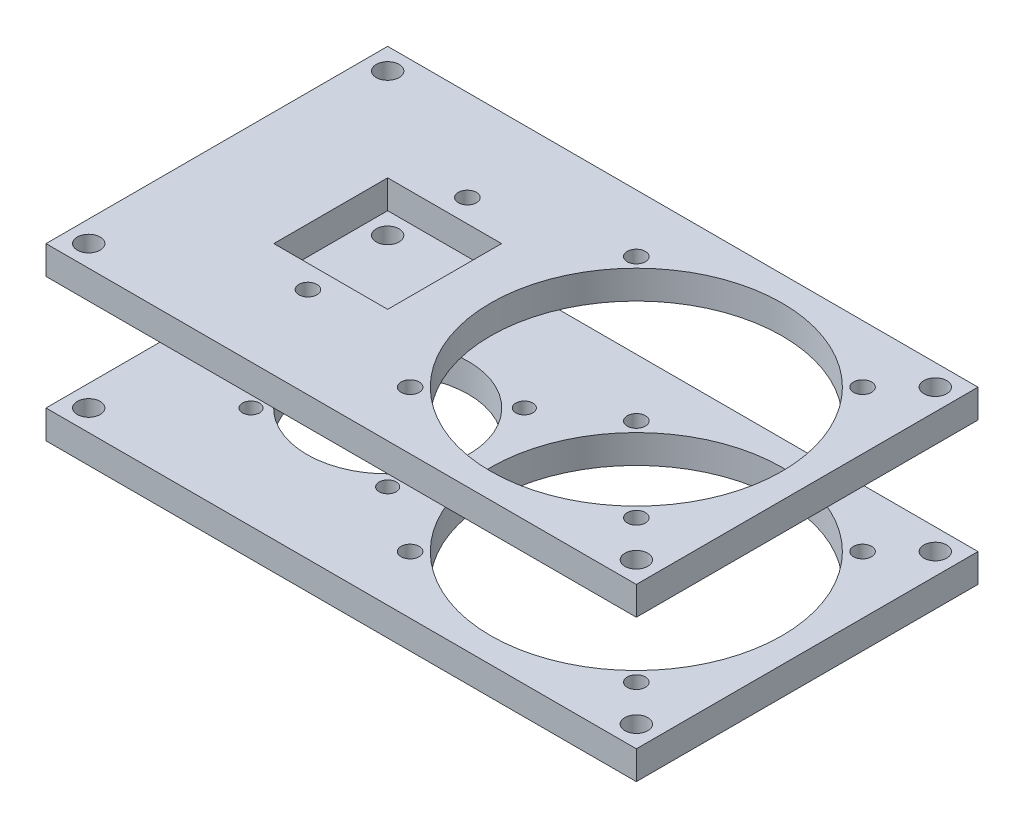
SolidWorks part; units mm, degrees
material "Alum Plate"
ref_plane "Front Plane" through (0, 0, 0) normal (0, 0, 1) x (1, 0, 0)
ref_plane "Top Plane" through (0, 0, 0) normal (0, 1, 0) x (1, 0, 0)
ref_plane "Right Plane" through (0, 0, 0) normal (1, 0, 0) x (0, 0, -1)
sketch "Sketch2" plane through (0, 0, 0) normal (0, 1, 0) x (1, 0, 0)
  line L0 (0, 0) -> (-55.4609, 0) construction
  line L2 (-93.5609, 38.1) -> (38.1, 38.1)
  line L3 (-93.5609, 38.1) -> (-93.5609, -38.1)
  line L4 (-93.5609, -38.1) -> (38.1, -38.1)
  line L5 (38.1, 38.1) -> (38.1, -38.1)
  line L6 (-93.5609, 38.1) -> (38.1, -38.1) construction
  line L7 (-93.5609, -38.1) -> (38.1, 38.1) construction
  line L8 (-68.1609, 12.7) -> (-42.7609, 12.7) construction
  line L9 (-68.1609, 12.7) -> (-68.1609, -12.7) construction
  line L10 (-68.1609, -12.7) -> (-42.7609, -12.7) construction
  line L11 (-42.7609, 12.7) -> (-42.7609, -12.7) construction
  line L12 (-68.1609, 12.7) -> (-42.7609, -12.7) construction
  line L13 (-68.1609, -12.7) -> (-42.7609, 12.7) construction
  circle A0 centre (0, 0) radius 32.5
  circle A1 centre (-55.4609, 0) radius 18 construction
  point P5 (-27.7305, 0)
  dimension "D1" = 65
  dimension "D2" = 36
  dimension "D3" = 55.4609
  dimension "D4" = 38.1
  dimension "D5" = 38.1
  dimension "D6" = 25.4
  dimension "D7" = 25.4
extrude "Boss-Extrude1" add sketch "Sketch2" against normal blind 6.35 from offset 19.05
mirror "Mirror1" about plane through (0, 0, 0) normal (0, 1, 0) of bodies 101
sketch "Sketch3" plane through (0, 19.05, 0) normal (0, 1, 0) x (1, 0, 0)
  line L1 (-68.1609, -12.7) -> (-42.7609, -12.7)
  line L2 (-68.1609, -12.7) -> (-68.1609, 12.7)
  line L3 (-68.1609, 12.7) -> (-42.7609, 12.7)
  line L4 (-42.7609, -12.7) -> (-42.7609, 12.7)
  line L5 (-68.1609, -12.7) -> (-42.7609, 12.7) construction
  line L6 (-68.1609, 12.7) -> (-42.7609, -12.7) construction
  point P4 (-55.4609, 0)
extrude "Cut-Extrude1" cut sketch "Sketch3" against normal up to next (6.35 mm away)
sketch "Sketch4" plane through (0, -19.05, 0) normal (0, -1, 0) x (1, 0, 0)
  circle A0 centre (-55.4609, 0) radius 18 construction
  circle A1 centre (-55.4609, 0) radius 18
extrude "Cut-Extrude2" cut sketch "Sketch4" against normal up to next (6.35 mm away)
sketch "Sketch5" plane through (0, -19.05, 0) normal (0, -1, 0) x (1, 0, 0)
  line L1 (-70.7009, 15.24) -> (-40.2209, 15.24) construction
  line L2 (-70.7009, 15.24) -> (-70.7009, -15.24) construction
  line L3 (-70.7009, -15.24) -> (-40.2209, -15.24) construction
  line L4 (-40.2209, 15.24) -> (-40.2209, -15.24) construction
  line L5 (-70.7009, 15.24) -> (-40.2209, -15.24) construction
  line L6 (-70.7009, -15.24) -> (-40.2209, 15.24) construction
  circle A0 centre (-70.7009, 15.24) radius 1.905
  circle A1 centre (-40.2209, 15.24) radius 1.905
  circle A2 centre (-40.2209, -15.24) radius 1.905
  circle A3 centre (-70.7009, -15.24) radius 1.905
  point P0 (-55.4609, 0)
  dimension "D2" = 3.81
  dimension "D1" = 30.48
extrude "Cut-Extrude3" cut sketch "Sketch5" against normal up to next (6.35 mm away)
sketch "Sketch6" plane through (0, 19.05, 0) normal (0, 1, 0) x (1, 0, 0)
  line L0 (-93.5609, -33.3375) -> (-88.7984, -33.3375) construction
  line L1 (-93.5609, 38.1) -> (-93.5609, -38.1) construction
  line L2 (-88.7984, -33.3375) -> (-88.7984, -38.1) construction
  line L3 (-93.5609, -38.1) -> (38.1, -38.1) construction
  line L4 (-93.5609, 33.3375) -> (-88.7984, 33.3375) construction
  line L5 (-88.7984, 33.3375) -> (-88.7984, 38.1) construction
  line L6 (38.1, 38.1) -> (-93.5609, 38.1) construction
  line L7 (38.1, 33.3375) -> (33.3375, 33.3375) construction
  line L8 (38.1, -38.1) -> (38.1, 38.1) construction
  line L9 (33.3375, 33.3375) -> (33.3375, 38.1) construction
  line L10 (33.3375, -38.1) -> (33.3375, -33.3375) construction
  line L11 (33.3375, -33.3375) -> (38.1, -33.3375) construction
  line L13 (25.226, 25.226) -> (-25.226, 25.226) construction
  line L14 (25.226, 25.226) -> (25.226, -25.226) construction
  line L15 (25.226, -25.226) -> (-25.226, -25.226) construction
  line L16 (-25.226, 25.226) -> (-25.226, -25.226) construction
  line L17 (25.226, 25.226) -> (-25.226, -25.226) construction
  line L18 (25.226, -25.226) -> (-25.226, 25.226) construction
  circle A0 centre (-88.7984, 33.3375) radius 2.5527
  circle A1 centre (33.3375, 33.3375) radius 2.5527
  circle A2 centre (33.3375, -33.3375) radius 2.5527
  circle A3 centre (-88.7984, -33.3375) radius 2.5527
  circle A4 centre (-25.226, 25.226) radius 2.0193
  circle A5 centre (25.226, 25.226) radius 2.0193
  circle A6 centre (25.226, -25.226) radius 2.0193
  circle A7 centre (-25.226, -25.226) radius 2.0193
  circle A8 centre (0, 0) radius 32.5 construction
  point P24 (0, 0)
  point P34 (-22.981, 22.981)
  point P35 (0, 0)
  point P36 (0, 0)
  dimension "D2" = 5.1054
  dimension "D3" = 4.0386
  dimension "D1" = 4.7625
  dimension "D4" = 3.175
extrude "Cut-Extrude4" cut sketch "Sketch6" against normal through all
sketch "Sketch7" plane through (0, 19.05, 0) normal (0, 1, 0) x (1, 0, 0)
  line L0 (-55.4609, 12.7) -> (-55.4609, 17.78) construction
  line L1 (-42.7609, 12.7) -> (-68.1609, 12.7) construction
  line L2 (-55.4609, -12.7) -> (-55.4609, -17.78) construction
  line L3 (-68.1609, -12.7) -> (-42.7609, -12.7) construction
  circle A0 centre (-55.4609, 17.78) radius 2.0193
  circle A1 centre (-55.4609, -17.78) radius 2.0193
  dimension "D1" = 4.0386
  dimension "D2" = 5.08
extrude "Cut-Extrude5" cut sketch "Sketch7" against normal up to next (6.35 mm away)
